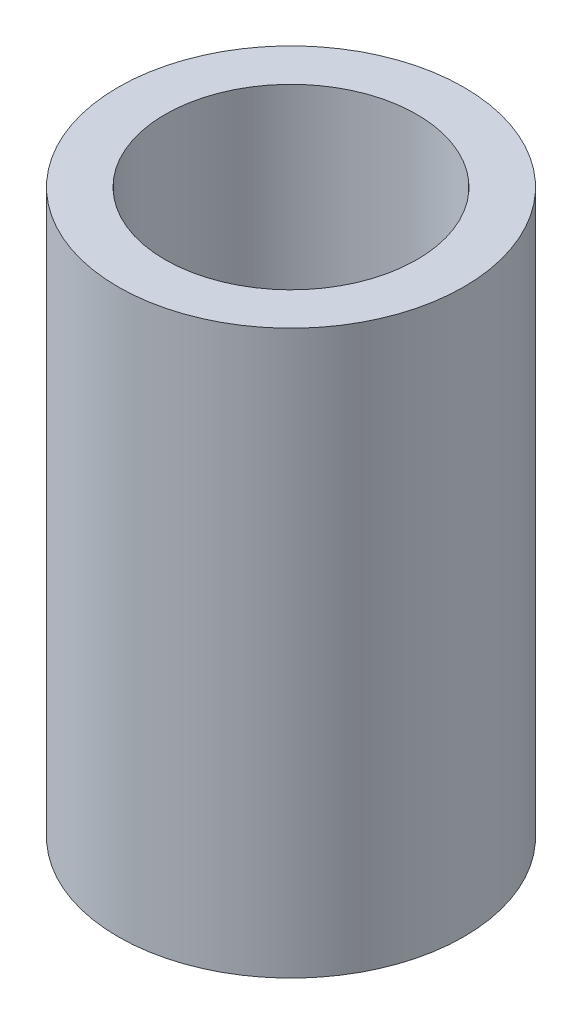
SolidWorks part; units mm, degrees
ref_plane "Front Plane" through (0, 0, 0) normal (0, 0, 1) x (1, 0, 0)
ref_plane "Top Plane" through (0, 0, 0) normal (0, 1, 0) x (1, 0, 0)
ref_plane "Right Plane" through (0, 0, 0) normal (1, 0, 0) x (0, 0, -1)
sketch "Sketch1" plane through (0, 0, 0) normal (0, 1, 0) x (1, 0, 0)
  circle A0 centre (0, 0) radius 20
  dimension "SLEEVE_OD" = 40
extrude "Boss-Extrude1" add sketch "Sketch1" along normal blind 65.1001
sketch "Sketch2" plane through (0, 0, 0) normal (0, 1, 0) x (1, 0, 0)
  circle A0 centre (0, 0) radius 14.5605
  dimension "BORE_D" = 29.1209
extrude "Cut-Extrude1" cut sketch "Sketch2" along normal through all
chamfer "Chamfer1" distance 3.7674 angle 30 rebuild error yes
